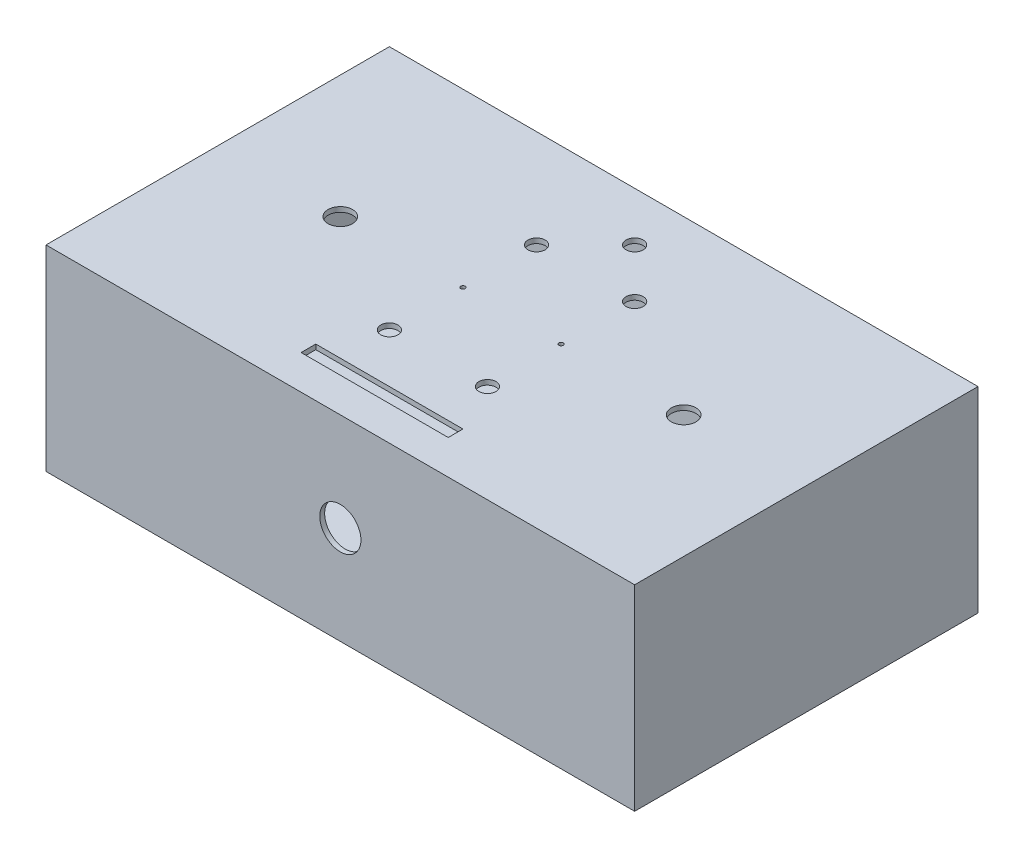
SolidWorks part; units mm, degrees
ref_plane "Front Plane" through (0, 0, 0) normal (0, 0, 1) x (1, 0, 0)
ref_plane "Top Plane" through (0, 0, 0) normal (0, 1, 0) x (1, 0, 0)
ref_plane "Right Plane" through (0, 0, 0) normal (1, 0, 0) x (0, 0, -1)
sketch "Sketch1" plane through (0, 0, 0) normal (0, 1, 0) x (1, 0, 0)
  line L1 (-152.4, 88.9) -> (152.4, 88.9)
  line L2 (-152.4, 88.9) -> (-152.4, -88.9)
  line L3 (-152.4, -88.9) -> (152.4, -88.9)
  line L4 (152.4, 88.9) -> (152.4, -88.9)
  dimension "D1" = 304.8
  dimension "D2" = 177.8
  dimension "D3" = 88.9
  dimension "D4" = 152.4
extrude "Boss-Extrude1" add sketch "Sketch1" along normal blind 101.6
shell "Shell1" thickness 2.54
sketch "Sketch3" plane through (0, 101.6, 0) normal (0, 1, 0) x (1, 0, 0)
  line L0 (0, -55) -> (0, 55) construction
  circle A0 centre (-88.9, 0) radius 6.35
  circle A1 centre (88.9, 0) radius 6.35
  dimension "D1" = 12.7
  dimension "D2" = 12.7
  dimension "D3" = 88.9
  dimension "D4" = 88.9
extrude "Cut-Extrude1" cut sketch "Sketch3" against normal blind 2.54
hole_wizard "#4-40 Tapped Hole1" positions "Sketch9" profile "Sketch8" tap size "#4-40" standard "ANSI Inch" end condition up to next
sketch "Sketch9" plane through (0, 101.6, 0) normal (0, 1, 0) x (1, 0, 0)
  line L0 (0, -55) -> (0, 55) construction
  point P0 (-25.4, 0)
  point P2 (25.4, 0)
  dimension "D1" = 25.4
  dimension "D2" = 25.4
sketch "Sketch8" plane through (-25.4, 101.6, 0) normal (1, 0, 0) x (0, 0, 1)
  line L0 (0, 0) -> (0, 2.54)
  line L1 (0, 2.54) -> (1.1303, 2.54)
  line L2 (1.1303, 2.54) -> (1.1303, 0)
  line L5 (1.1303, 0) -> (0, 0)
  line L11 (0, -6.35) -> (0, 107.95) construction
  dimension "Thread Major Dia." = 2.2606
  dimension "Thru Tap Drill Depth" = 2.54
sketch "Sketch10" plane through (0, 101.6, 0) normal (0, 1, 0) x (1, 0, 0)
  line L1 (-29.0322, 16.1544) -> (29.0322, 16.1544)
  line L2 (-29.0322, 16.1544) -> (-29.0322, -16.1544)
  line L3 (-29.0322, -16.1544) -> (29.0322, -16.1544)
  line L4 (29.0322, 16.1544) -> (29.0322, -16.1544)
  dimension "D1" = 16.1544
  dimension "D2" = 32.3088
  dimension "D3" = 29.0322
  dimension "D4" = 58.0644
sketch "Sketch11" plane through (0, 101.6, 0) normal (0, 1, 0) x (1, 0, 0)
  line L0 (0, -55) -> (0, 55) construction
  line L1 (-55, 0) -> (55, 0) construction
  circle A0 centre (-25.4, 38.1) radius 4.445
  circle A1 centre (25.4, 38.1) radius 4.445
  circle A2 centre (25.4, -38.1) radius 4.445
  circle A3 centre (-25.4, -38.1) radius 4.445
  dimension "D1" = 8.89
  dimension "D2" = 25.4
  dimension "D3" = 25.4
  dimension "D4" = 38.1
  dimension "D5" = 76.2
extrude "Cut-Extrude2" cut sketch "Sketch11" against normal blind 2.54
sketch "Sketch12" plane through (0, 101.6, 0) normal (0, 1, 0) x (1, 0, 0)
  line L0 (-55, 0) -> (55, 0) construction
  line L2 (-38.1, -63.5) -> (38.1, -63.5)
  line L3 (-38.1, -63.5) -> (-38.1, -71.12)
  line L4 (-38.1, -71.12) -> (38.1, -71.12)
  line L5 (38.1, -63.5) -> (38.1, -71.12)
  circle A0 centre (0, 63.5) radius 4.445
  dimension "D6" = 8.89
  dimension "D1" = 63.5
  dimension "D2" = 63.5
  dimension "D3" = 7.62
  dimension "D4" = 76.2
  dimension "D5" = 38.1
extrude "Cut-Extrude3" cut sketch "Sketch12" against normal blind 2.54
sketch "Sketch13" plane through (0, 0, 88.9) normal (0, 0, 1) x (1, 0, 0)
  line L0 (-152.4, 101.6) -> (-152.4, 0) construction
  circle A0 centre (0, 50.8) radius 10.6594
  point P2 (-152.4, 50.8)
  dimension "D1" = 0
extrude "Cut-Extrude4" cut sketch "Sketch13" against normal blind 2.54
